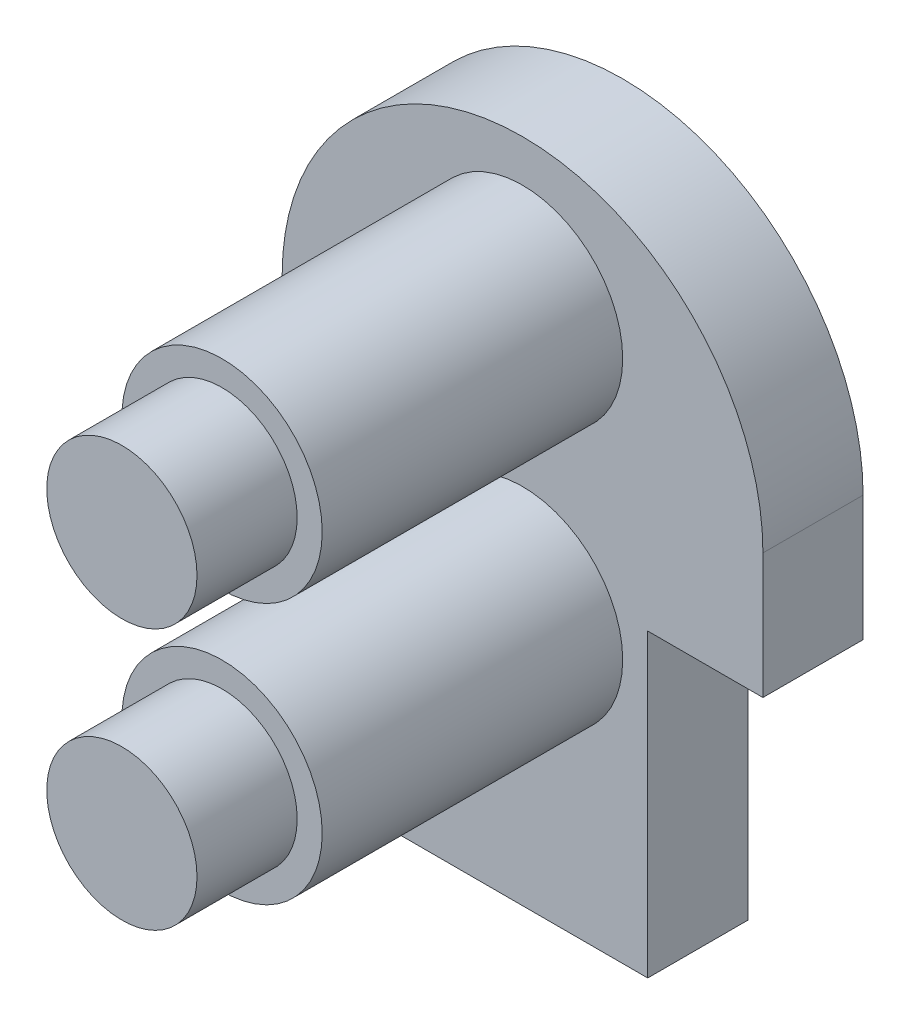
SolidWorks part; units mm, degrees
ref_plane "Front Plane" through (0, 0, 0) normal (0, 0, 1) x (1, 0, 0)
ref_plane "Top Plane" through (0, 0, 0) normal (0, 1, 0) x (1, 0, 0)
ref_plane "Right Plane" through (0, 0, 0) normal (1, 0, 0) x (0, 0, -1)
sketch "Sketch1" plane through (0, 0, 0) normal (0, 0, 1) x (1, 0, 0)
  line L0 (0, 0) -> (10, 0)
  line L1 (0, 0) -> (0, 4)
  line L2 (0, 4) -> (-2.5, 4)
  line L3 (3.3546, 18.0712) -> (6.6454, 18.0712) construction
  line L4 (-2.5, 4) -> (-2.5, 8)
  line L5 (-2.5, 8) -> (0, 8)
  line L6 (0, 8) -> (0, 12)
  line L7 (5, 0) -> (5, 27) construction
  line L8 (10, 0) -> (10, 4)
  line L9 (10, 4) -> (12.5, 4)
  line L10 (12.5, 4) -> (12.5, 8)
  line L11 (12.5, 8) -> (10, 8)
  line L12 (3.3546, 23.7712) -> (1.7091, 20.9212) construction
  line L13 (8.2909, 10.5) -> (6.6454, 13.35) construction
  line L14 (6.6454, 13.35) -> (3.3546, 13.35) construction
  line L15 (3.3546, 13.35) -> (1.7091, 10.5) construction
  line L16 (1.7091, 10.5) -> (3.3546, 7.65) construction
  line L17 (3.3546, 7.65) -> (6.6454, 7.65) construction
  line L18 (6.6454, 7.65) -> (8.2909, 10.5) construction
  line L19 (1.7091, 20.9212) -> (3.3546, 18.0712) construction
  line L20 (0, 12) -> (-4.6, 12)
  line L21 (10, 8) -> (10, 12)
  line L22 (6.6454, 18.0712) -> (8.2909, 20.9212) construction
  line L23 (8.2909, 20.9212) -> (6.6454, 23.7712) construction
  line L24 (6.6454, 23.7712) -> (3.3546, 23.7712) construction
  line L25 (10, 12) -> (14.6, 12)
  line L26 (-4.6, 12) -> (-4.6, 17)
  line L27 (14.6, 12) -> (14.6, 17)
  line L28 (3.3546, 13.35) -> (6.6454, 7.65) construction
  line L29 (6.6454, 13.35) -> (3.3546, 7.65) construction
  line L30 (3.3546, 18.0712) -> (6.6454, 23.7712) construction
  line L31 (3.3546, 23.7712) -> (6.6454, 18.0712) construction
  circle A0 centre (5, 20.9212) radius 3.2909 construction
  arc A1 (14.6, 17) -> (-4.6, 17) centre (5, 17) ccw
  circle A2 centre (5, 10.5) radius 3.2909 construction
  dimension "D5" = 2.5
  dimension "D9" = 4
  dimension "D10" = 4
  dimension "D12" = 2.5
  dimension "D8" = 4.6
  dimension "D2" = 5.7
extrude "Boss-Extrude1" add sketch "Sketch1" along normal blind 4
sketch "Sketch2" plane through (0, 0, 4) normal (0, 0, 1) x (1, 0, 0)
  line L0 (-2.5, 8) -> (0, 8)
  line L1 (0, 8) -> (0, 4)
  line L2 (0, 4) -> (-2.5, 4)
  line L3 (-2.5, 4) -> (-2.5, 8)
  line L4 (10, 8) -> (12.5, 8)
  line L5 (12.5, 8) -> (12.5, 4)
  line L6 (12.5, 4) -> (10, 4)
  line L7 (10, 4) -> (10, 8)
extrude "Cut-Extrude1" cut sketch "Sketch2" against normal up to surface (4 mm away) up to face at (5, 8.725, 0)
sketch "Sketch4" plane through (0, 0, 0) normal (0, 0, 1) x (1, 0, 0)
  circle A0 centre (5, 20.9212) radius 4
  circle A2 centre (5, 10.5) radius 4
  dimension "D3" = 8
  dimension "D1" = 10.5
  dimension "D2" = 5
  dimension "D4" = 10.4212
extrude "Boss-Extrude2" add sketch "Sketch4" along normal blind 16
sketch "Sketch5" plane through (0, 0, 16) normal (0, 0, 1) x (1, 0, 0)
  circle A0 centre (5, 10.5) radius 3
  circle A1 centre (5, 20.9212) radius 3
  dimension "D1" = 6
extrude "Boss-Extrude3" add sketch "Sketch5" along normal blind 4
equation "\"D8@Sketch1\"= 5 - \"tol2@parametersSketch@prostheticParameters.SLDPRT\""
